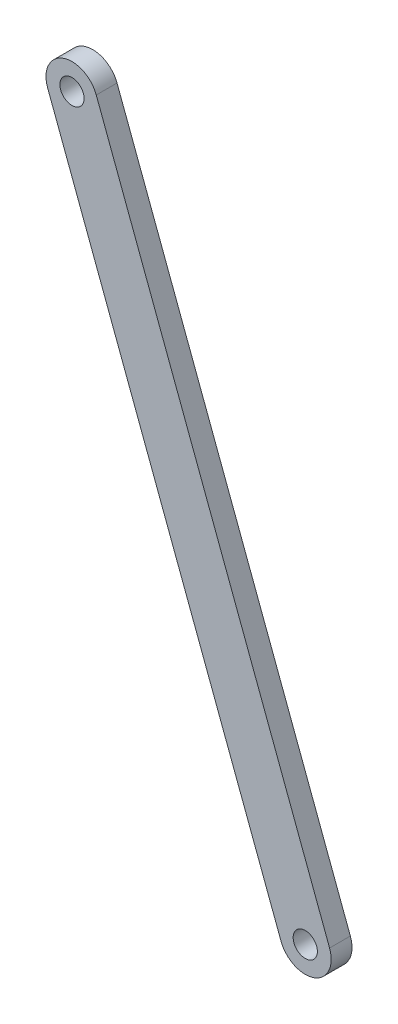
SolidWorks part; units mm, degrees
ref_plane "Front" through (0, 0, 0) normal (0, 0, 1) x (1, 0, 0)
ref_plane "Top" through (0, 0, 0) normal (0, 1, 0) x (1, 0, 0)
ref_plane "Right" through (0, 0, 0) normal (1, 0, 0) x (0, 0, -1)
sketch "Body Driving Dimensions" plane through (0, 0, 0) normal (0, 0, 1) x (1, 0, 0)
  line L0 (0, 0) -> (67.4255, -79.1821)
  line L1 (67.4255, -79.1821) -> (0, -258.9536)
  line L2 (0, -258.9536) -> (-67.4255, -79.1821)
  line L3 (-67.4255, -79.1821) -> (0, 0)
  line L4 (0, 0) -> (0, -36.971) construction
  line L5 (0, 0) -> (126.3939, 57.841)
  line L6 (126.3939, 57.841) -> (67.4255, -79.1821)
  line L7 (0, 0) -> (-126.3939, 57.841)
  line L8 (-126.3939, 57.841) -> (-67.4255, -79.1821)
  line L9 (126.3939, 57.841) -> (215.514, 98.6245) construction
  line L10 (-126.3939, 57.841) -> (-215.514, 98.6245) construction
  line L11 (126.3939, 57.841) -> (126.3939, 26.1689) construction
  line L12 (-126.3939, 57.841) -> (-126.3939, 26.1689) construction
  line L13 (0, 0) -> (-98.8336, -98.8336) construction
  line L14 (0, 0) -> (98.8336, -98.8336) construction
  dimension "D1" = 45
  dimension "D2" = 45
  dimension "D3" = 192
  dimension "D4" = 104
  dimension "D5" = 139
  dimension "D6" = 139
  dimension "D7" = 114.59
  dimension "D8" = 114.59
sketch "Sketch1" plane through (0, 0, 0) normal (0, 0, 1) x (1, 0, 0)
  line L0 (-67.4255, -79.1821) -> (0, -258.9536) construction
  line L1 (-60.4032, -76.5483) -> (7.0223, -256.3198)
  line L2 (-74.4478, -81.8159) -> (-7.0223, -261.5874)
  circle A0 centre (-67.4255, -79.1821) radius 3.5
  circle A1 centre (0, -258.9536) radius 3.5
  arc A2 (-60.4032, -76.5483) -> (-74.4478, -81.8159) centre (-67.4255, -79.1821) ccw
  arc A3 (-7.0223, -261.5874) -> (7.0223, -256.3198) centre (0, -258.9536) ccw
  point P6 (-33.7127, -169.0679)
  dimension "D1" = 7
  dimension "D2" = 7.5
extrude "Tibya" add sketch "Sketch1" along normal blind 6
sketch "Sketch2" [suppressed] plane through (0, 0, 0) normal (0, 0, 1) x (1, 0, 0)
  line L0 (0, 0) -> (104, 0) construction
  line L1 (0, 0) -> (67.4255, -79.1821) construction
  line L2 (104.6537, 7.4715) -> (14.303, 15.3761)
  line L4 (104.6537, -7.4715) -> (14.303, -15.3761)
  circle A0 centre (0, 0) radius 17.5 construction
  circle A1 centre (0, 17.5) radius 1.65
  circle A2 centre (-17.5, 0) radius 1.65
  circle A3 centre (17.5, 0) radius 1.65
  circle A4 centre (0, -17.5) radius 1.65
  circle A5 centre (104, 0) radius 3.5
  circle A6 centre (104, 0) radius 7.5 construction
  circle A7 centre (0, 0) radius 21 construction
  arc A8 (104.6537, 7.4715) -> (104.6537, -7.4715) centre (104, 0) cw
  arc A9 (14.303, 15.3761) -> (14.303, -15.3761) centre (0, 0) ccw
  circle A10 centre (0, 0) radius 7
  dimension "D1" = 3.3
  dimension "D2" = 35
  dimension "D3" = 7
  dimension "D4" = 42
  dimension "D5" = 15
  dimension "D6" = 14
  dimension "D7" = 5
extrude "Boss-Extrude2" [suppressed] add sketch "Sketch2" along normal blind 6
fillet "Fillet1" [suppressed] radius 5
sketch "Sketch4" [suppressed] plane through (0, 0, 0) normal (1, 0, 0) x (0, 0, -1)
  line L0 (27.75, 0) -> (-27.75, 0)
  point P4 (0, 0)
  dimension "D1" = 55.5
sketch "Sketch5" [suppressed] plane through (0, 0, 0) normal (0, 1, 0) x (1, 0, 0)
  circle A0 centre (0, 0) radius 3.5
  circle A2 centre (0, 0) radius 3.25
  dimension "D1" = 7
  dimension "D2" = 0.25
extrude "Boss-Extrude3" [suppressed] add sketch "Sketch5" against normal blind 304
sketch "Sketch6" [suppressed] plane through (0, 0, 0) normal (0, 0, 1) x (1, 0, 0)
  line L0 (-18.9268, 67.3927) -> (-132.3071, 35.5506) construction
  line L1 (5.7655, 69.7622) -> (149.1516, 57.912) construction
  circle A0 centre (0, 0) radius 70 construction
  circle A1 centre (0, 0) radius 160 construction
  circle A2 centre (0, 0) radius 137 construction
sketch "Sketch8" [suppressed] plane through (0, 0, 0) normal (0, 0, 1) x (1, 0, 0)
  line L0 (0, 0) -> (0, 177) construction
  line L1 (50, 177) -> (-50, 177)
  line L2 (-50, 177) -> (-147.759, 39.7025)
  line L3 (0, 177) -> (0, 137) construction
  line L4 (-132.3071, 35.5506) -> (-228.8899, 61.5022) construction
  line L5 (-147.759, 39.7025) -> (-147.759, 14.7025)
  line L6 (-147.759, 14.7025) -> (-25.3303, -48.8199)
  line L7 (0, 0) -> (-132.3071, 35.5506) construction
  line L8 (149.1516, 57.912) -> (242.3794, 94.1101) construction
  line L9 (50, 177) -> (164.0668, 63.7032)
  line L10 (164.0668, 63.7032) -> (164.0668, 38.7032)
  line L11 (164.0668, 38.7032) -> (29.4025, -46.4811)
  line L12 (40, 169.5) -> (-40, 169.5) construction
  line L13 (40, 119.5) -> (-40, 119.5) construction
  circle A0 centre (0, 0) radius 55 construction
  circle A1 centre (0, 0) radius 160 construction
  circle A2 centre (0, 0) radius 45
  arc A3 (-25.3303, -48.8199) -> (29.4025, -46.4811) centre (0, 0) ccw
  circle A4 centre (-40, 169.5) radius 2.65
  circle A5 centre (0, 0) radius 137 construction
  circle A6 centre (40, 169.5) radius 2.65
  circle A7 centre (0, 169.5) radius 2.65
  circle A8 centre (40, 119.5) radius 2.65
  circle A9 centre (0, 119.5) radius 2.65
  circle A10 centre (-40, 119.5) radius 2.65
  point P12 (0, 160)
  point P26 (0, 169.5)
  point P37 (0, 119.5)
  dimension "D2" = 110
  dimension "D3" = 90
  dimension "D10" = 5.3
  dimension "D4" = 16
  dimension "D5" = 16
  dimension "D6" = 25
  dimension "D1" = 100
  dimension "D8" = 10
  dimension "D9" = 7.5
  dimension "D11" = 80
  dimension "D12" = 50
  dimension "D7" = 135
  dimension "D13" = 40
extrude "Boss-Extrude4" [suppressed] add sketch "Sketch8" along normal blind 6
sketch "Sketch9" [suppressed] plane through (0, 0, 0) normal (0, 0, -1) x (-1, 0, 0)
  line L0 (0, 0) -> (35.3553, -35.3553) construction
  line L1 (0, 0) -> (0, -36.971) construction
  circle A0 centre (0, 0) radius 50 construction
  circle A1 centre (35.3553, -35.3553) radius 1.65
  circle A2 centre (-35.3553, -35.3553) radius 1.65
  circle A3 centre (-35.3553, 35.3553) radius 1.65
  circle A4 centre (35.3553, 35.3553) radius 1.65
  point P16 (0, 0)
  dimension "D1" = 100
  dimension "D3" = 3.3
  dimension "D2" = 45
  dimension "D4" = 4
extrude "Cut-Extrude1" [suppressed] cut sketch "Sketch9" against normal through all
sketch "Sketch10" [suppressed] plane through (0, 0, 0) normal (0, 0, -1) x (-1, 0, 0)
  line L0 (45, 31.6228) -> (45, 163.3332)
  line L1 (45, 163.3332) -> (138.488, 32.034)
  line L2 (138.488, 32.034) -> (54.1935, 9.3843)
  line L3 (0, 55) -> (0, 163.3332) construction
  line L4 (50, 177) -> (147.759, 39.7025) construction
  line L5 (132.3071, 35.5506) -> (228.8899, 61.5022) construction
  line L6 (-52.8683, 15.1638) -> (-154.4619, 54.6102)
  line L7 (-154.4619, 54.6102) -> (-45, 163.3332)
  line L8 (-45, 163.3332) -> (-45, 31.6228)
  line L9 (-149.1516, 57.912) -> (-242.3794, 94.1101) construction
  line L10 (-164.0668, 63.7032) -> (-50, 177) construction
  line L11 (-45, 163.3332) -> (45, 163.3332) construction
  line L12 (0, 55) -> (0, 0) construction
  circle A0 centre (0, 0) radius 55 construction
  arc A1 (54.1935, 9.3843) -> (45, 31.6228) centre (0, 0) ccw
  arc A2 (-45, 31.6228) -> (-52.8683, 15.1638) centre (0, 0) ccw
  point P19 (0, 163.3332)
  dimension "D1" = 110
  dimension "D4" = 5
  dimension "D5" = 5
  dimension "D3" = 12
  dimension "D2" = 90
  dimension "D6" = 13.2201
extrude "Cut-Extrude2" [suppressed] cut sketch "Sketch10" against normal through all
fillet "Fillet2" [suppressed] radius 10
fillet "Fillet3" [suppressed] radius 5
sketch "Sketch11" [suppressed] plane through (0, 0, 0) normal (0, 0, -1) x (-1, 0, 0)
  circle A0 centre (142.759, 38.1043) radius 1.6
  circle A1 centre (142.759, 17.7412) radius 1.6
  circle A2 centre (-159.0668, 61.6222) radius 1.6
  circle A3 centre (-159.0668, 41.4567) radius 1.6
  dimension "D1" = 3.2
  dimension "D2" = 20.3631
extrude "Cut-Extrude3" [suppressed] cut sketch "Sketch11" against normal through all
sketch "Sketch12" [suppressed] plane through (0, 0, 0) normal (0, 0, -1) x (-1, 0, 0)
  line L0 (214.1882, 56.4553) -> (214.1882, 37.1954) construction
  line L1 (219.1882, 56.4553) -> (219.1882, 37.1954)
  line L2 (209.1882, 56.4553) -> (209.1882, 37.1954)
  line L4 (203.7362, 54.7434) -> (228.8899, 61.5022) construction
  arc A0 (219.1882, 56.4553) -> (209.1882, 56.4553) centre (214.1882, 56.4553) ccw
  arc A1 (209.1882, 37.1954) -> (219.1882, 37.1954) centre (214.1882, 37.1954) ccw
  arc A2 (219.1882, 56.4553) -> (217.2648, 60.3967) centre (214.1882, 56.4553) ccw construction
  circle A3 centre (203.7362, 54.7434) radius 2.5
  circle A4 centre (203.7362, 54.7434) radius 6.5
  circle A5 centre (214.1882, 56.4553) radius 2.55
  circle A6 centre (203.7362, 54.7434) radius 4.5 construction
  point P4 (214.1882, 46.8254)
  dimension "D2" = 5
  dimension "D3" = 13
  dimension "D4" = 5.1
  dimension "D5" = 9
sketch "Sketch13" [suppressed] plane through (0, 0, 0) normal (0, 0, -1) x (-1, 0, 0)
  line L0 (209.1882, 56.4553) -> (209.1882, 37.1954) construction
  line L1 (219.1882, 56.4553) -> (219.1882, 37.1954) construction
  line L2 (209.1882, 56.4553) -> (209.1882, 37.1954)
  line L3 (219.1882, 56.4553) -> (219.1882, 37.1954)
  arc A0 (219.1882, 56.4553) -> (209.1882, 56.4553) centre (214.1882, 56.4553) ccw construction
  arc A1 (219.1882, 56.4553) -> (209.1882, 56.4553) centre (214.1882, 56.4553) ccw
  arc A2 (209.1882, 37.1954) -> (219.1882, 37.1954) centre (214.1882, 37.1954) ccw construction
  arc A3 (209.1882, 37.1954) -> (219.1882, 37.1954) centre (214.1882, 37.1954) ccw
extrude "Boss-Extrude5" [suppressed] add sketch "Sketch13" along normal blind 80.5 separate body
delete or keep bodies "Body-Delete/Keep 1" [suppressed] type delete bodies bodies 107
sketch "Sketch14" [suppressed] plane through (0, 0, -80.5) normal (0, 0, -1) x (-1, 0, 0)
  circle A0 centre (214.1882, 56.4553) radius 2.85
  circle A1 centre (214.1882, 37.1954) radius 2.85
  dimension "D1" = 5.7
extrude "Cut-Extrude4" [suppressed] cut sketch "Sketch14" against normal blind 8
ref_plane "Plane1" [suppressed] through (0, 0, -40.25) normal (0, 0, -1) x (-1, 0, 0)
mirror "Mirror1" [suppressed] about plane through (0, 0, -40.25) normal (0, 0, -1)
ref_plane "Plane2" [suppressed] through (0, 0, -31.9) normal (0, 0, 1) x (1, 0, 0)
sketch "Sketch15" [suppressed] plane through (0, 0, -31.9) normal (0, 0, 1) x (1, 0, 0)
  line L3 (-210.2362, 54.7434) -> (-203.7362, 54.7434) construction
  line L5 (-203.6047, 61.2421) -> (-214.087, 61.4543)
  line L6 (-203.6047, 48.2448) -> (-209.1882, 48.1317)
  line L7 (-209.1882, 56.4553) -> (-209.1882, 37.1954) construction
  line L8 (-209.1882, 48.1317) -> (-214.087, 61.4543)
  circle A0 centre (-203.7362, 54.7434) radius 6.5 construction
  arc A2 (-203.6047, 61.2421) -> (-203.6047, 48.2448) centre (-203.7362, 54.7434) cw
  circle A3 centre (-203.7362, 54.7434) radius 4
  arc A4 (-209.1882, 56.4553) -> (-219.1882, 56.4553) centre (-214.1882, 56.4553) ccw construction
  dimension "D3" = 8
  dimension "D1" = 1.16
  dimension "D2" = 1.16
extrude "Boss-Extrude6" [suppressed] add sketch "Sketch15" along normal blind 5.5 and the other way blind 5.5
sketch "Sketch16" [suppressed] plane through (0, 0, -31.9) normal (0, 0, 1) x (1, 0, 0)
  circle A0 centre (-203.7362, 54.7434) radius 6.5
  circle A1 centre (-203.7362, 54.7434) radius 6.5 construction
extrude "Cut-Extrude5" [suppressed] cut sketch "Sketch16" against normal blind 1 and the other way blind 1
fillet "Fillet5" [suppressed] radius 5
chamfer "Chamfer1" [suppressed] distance 0.5 angle 70
sketch "Sketch17" [suppressed] plane through (0, 0, 0) normal (0, 0, 1) x (1, 0, 0)
  line L0 (0, 0) -> (-45, 0) construction
  line L1 (0, 0) -> (0, 45) construction
  line L2 (0, 0) -> (-35.3553, 35.3553) construction
  line L3 (0, 0) -> (0, 170) construction
  line L4 (54, 170) -> (-54, 170)
  line L5 (-54, 170) -> (-54, 0)
  line L6 (54, 0) -> (54, 170)
  line L7 (45, 162.5) -> (-45, 162.5) construction
  line L8 (45, 112.5) -> (-45, 112.5) construction
  circle A0 centre (0, 0) radius 45
  circle A1 centre (-35.3553, 35.3553) radius 1.65
  circle A2 centre (35.3553, 35.3553) radius 1.65
  circle A3 centre (35.3553, -35.3553) radius 1.65
  circle A4 centre (-35.3553, -35.3553) radius 1.65
  circle A5 centre (0, 0) radius 54 construction
  circle A6 centre (0, 162.5) radius 2.65
  arc A7 (-54, 0) -> (54, 0) centre (0, 0) ccw
  circle A8 centre (-45, 162.5) radius 2.65
  circle A9 centre (45, 162.5) radius 2.65
  circle A10 centre (-45, 112.5) radius 2.65
  circle A11 centre (-35.3553, 35.3553) radius 4 construction
  circle A12 centre (0, 112.5) radius 2.65
  circle A13 centre (45, 112.5) radius 2.65
  point P16 (0, 0)
  point P19 (0, 170)
  point P25 (0, 162.5)
  point P33 (0, 112.5)
  dimension "D1" = 90
  dimension "D4" = 3.3
  dimension "D6" = 170
  dimension "D9" = 5.3
  dimension "D11" = 8
  dimension "D7" = 50
  dimension "D2" = 45
  dimension "D3" = 50
  dimension "D8" = 90
  dimension "D10" = 7.5
  dimension "D5" = 4
extrude "Simple Side Plate" [suppressed] add sketch "Sketch17" along normal blind 6
fillet "Fillet7" [suppressed] radius 2.5
equation "\"l2\"= 192"
equation "\"D3@Body Driving Dimensions\" = \"l2\""
equation "\"l1\"= 104"
equation "\"D4@Body Driving Dimensions\" = \"l1\""
equation "\"s1r\"= 2rad"
equation "\"s2r\"= - 2rad"
equation "\"offset\"= 10mm"
equation "\"s1_len\"= 0.025m"
equation "\"s2_len\"= 0.025m"
equation "\"s1_anchor_dist\"= \"offset\" + \"l1\" + \"s1_len\""
equation "\"s2_anchor_dist\"= \"offset\" + \"l1\" + \"s2_len\"'this was: = \"offset\" + \"l1\" + \"s2_len\""
equation "\"D5@Body Driving Dimensions\" = \"s1_anchor_dist\""
equation "\"D6@Body Driving Dimensions\" = \"s2_anchor_dist\""
equation "\"D7@Body Driving Dimensions\" = \"s1r\""
equation "\"D8@Body Driving Dimensions\" =  - \"s2r\""
equation "\"carbon_fiber_plate_thickness\"=6"
equation "\"D1@Tibya\" = \"carbon_fiber_plate_thickness\""
equation "\"D1@Boss-Extrude2\"=\"carbon_fiber_plate_thickness\""
equation "\"motor_to_motor_spacing\"= 55.5"
equation "\"D1@Sketch4\"=\"motor_to_motor_spacing\""
equation "\"D1@Boss-Extrude3\"=\"l1\"+\"l2\" + 8"
equation "\"D5@Sketch8\"=\"D4@Sketch8\""
equation "\"D5@Sketch10\"=\"D4@Sketch10\""
equation "\"D2@Sketch15\"=\"D1@Sketch15\""
equation "\"D7@Sketch8\"=\"l2\" - \"l1\" + 47"
